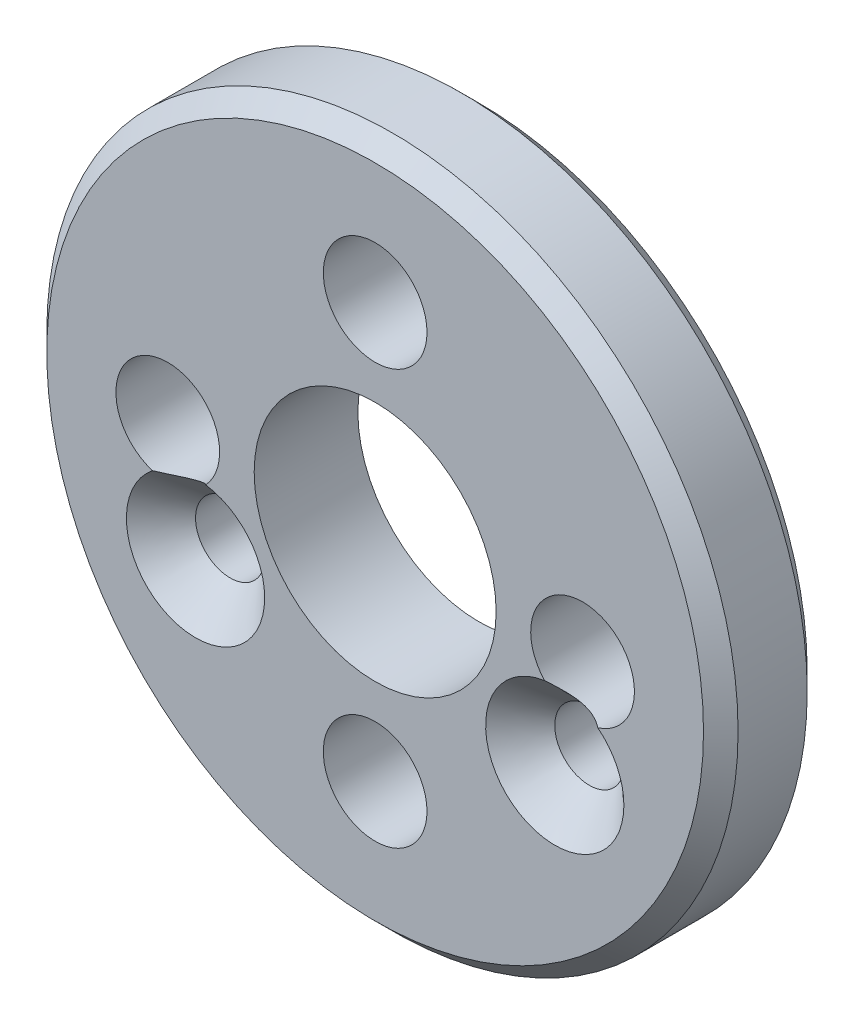
SolidWorks part; units mm, degrees
ref_plane "前视基准面" through (0, 0, 0) normal (0, 0, 1) x (1, 0, 0)
ref_plane "上视基准面" through (0, 0, 0) normal (0, 1, 0) x (1, 0, 0)
ref_plane "右视基准面" through (0, 0, 0) normal (1, 0, 0) x (0, 0, -1)
sketch "草图1" plane through (0, 0, 0) normal (0, 0, 1) x (1, 0, 0)
  line L0 (-10.134, 0) -> (10.3365, 0) construction
  line L1 (0, 10.1135) -> (0, -8.3696) construction
  circle A0 centre (0, 6) radius 1
  circle A1 centre (5.1962, -3) radius 1
  circle A2 centre (-5.1962, -3) radius 1
  circle A3 centre (0, 0) radius 10
  circle A4 centre (0, 6) radius 1.5
  circle A5 centre (0, 0) radius 3.5
  circle A6 centre (6, 0) radius 1.5
  circle A7 centre (0, -6) radius 1.5
  circle A8 centre (-6, 0) radius 1.5
  point P6 (0, 0)
  point P24 (0, 0)
  dimension "D1" = 2
  dimension "D3" = 20
  dimension "D4" = 7
  dimension "D5" = 3
  dimension "D2" = 6
  dimension "D6" = 6
extrude "凸台-拉伸1" add sketch "草图1" along normal blind 3 contours A3 A8 A7 A6 A5 A4 A1 A2 region at (-9.7172, 0, 0)
chamfer "倒角1" distance 0.5 angle 45 2 edges at (10, 0, 0) (10, 0, 3)
chamfer "倒角2" distance 1 angle 45 2 edges at (6.1962, -3, 3) (-4.1962, -3, 3)
